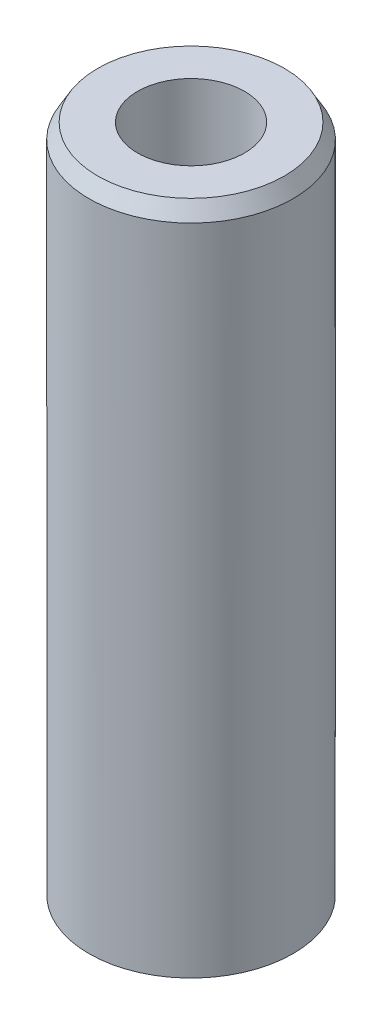
SolidWorks part; units mm, degrees
ref_plane "Front Plane" through (0, 0, 0) normal (0, 0, 1) x (1, 0, 0)
ref_plane "Top Plane" through (0, 0, 0) normal (0, 1, 0) x (1, 0, 0)
ref_plane "Right Plane" through (0, 0, 0) normal (1, 0, 0) x (0, 0, -1)
sketch "Sketch1" plane through (0, 0, 0) normal (0, 1, 0) x (1, 0, 0)
  circle A0 centre (0, 0) radius 30
  dimension "SHAFT_OD" = 60
extrude "Boss-Extrude1" add sketch "Sketch1" along normal blind 199.1922
sketch "Sketch2" plane through (0, 0, 0) normal (0, 1, 0) x (1, 0, 0)
  circle A0 centre (0, 0) radius 15.721
  dimension "BORE_D" = 31.4421
extrude "Cut-Extrude1" cut sketch "Sketch2" along normal through all
chamfer "Chamfer1" distance 4.4738 angle 30 2 edges at (0, 199.1922, 30) (0, 0, 30) first distance on face at (0, 199.1922, 30) first distance on face at (0, 0, 15.721)
